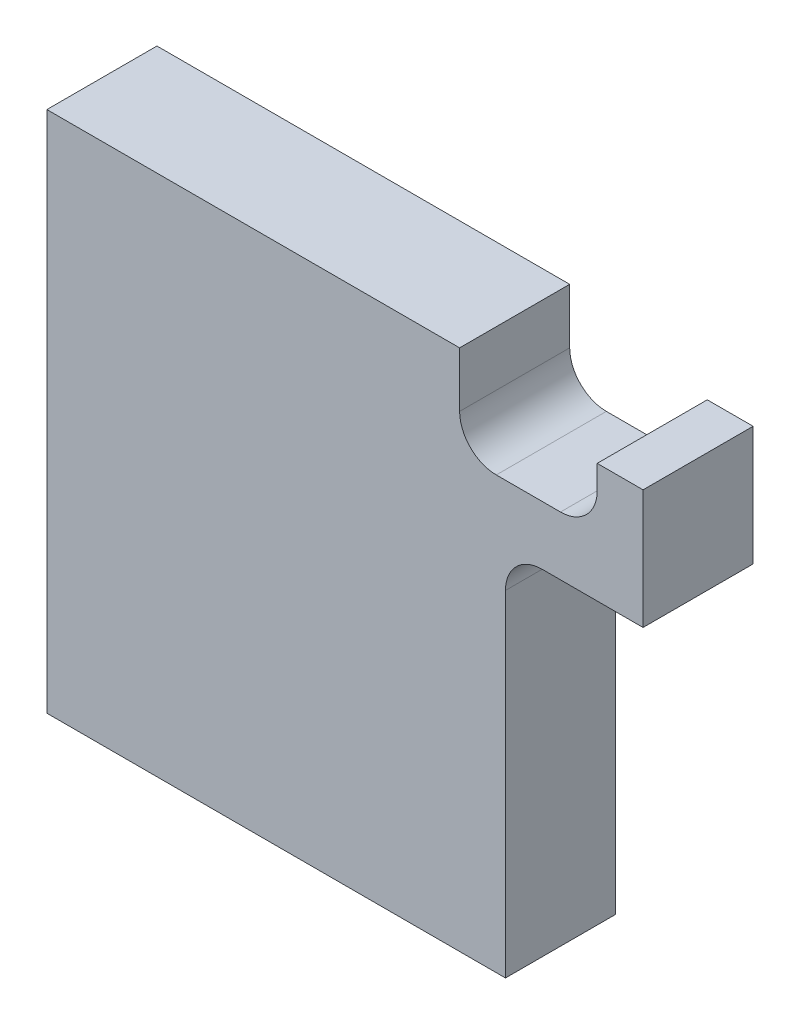
SolidWorks part; units mm, degrees
ref_plane "前视基准面" through (0, 0, 0) normal (0, 0, 1) x (1, 0, 0)
ref_plane "上视基准面" through (0, 0, 0) normal (0, 1, 0) x (1, 0, 0)
ref_plane "右视基准面" through (0, 0, 0) normal (1, 0, 0) x (0, 0, -1)
sketch "草图1" plane through (0, 0, 0) normal (0, 0, 1) x (1, 0, 0)
  line L0 (4.2193, 10.5) -> (4.2193, 4.8)
  line L1 (4.2193, 10.5) -> (8.7193, 10.5)
  line L2 (8.7193, 10.5) -> (8.7193, 9.5)
  line L3 (8.7193, 9.5) -> (10.2193, 9.5)
  line L4 (10.2193, 9.5) -> (10.2193, 10.1595)
  line L5 (10.2193, 10.1595) -> (10.7193, 10.1595)
  line L6 (10.7193, 10.1595) -> (10.7193, 8.8595)
  line L7 (9.2193, 4.8) -> (4.2193, 4.8)
  line L10 (10.7193, 8.8595) -> (9.2193, 8.8595)
  line L11 (9.2193, 8.8595) -> (9.2193, 4.8)
  line L13 (10.2193, 9.5) -> (10.2193, 8.8595) construction
  dimension "D1" = 1.3
  dimension "D2" = 0.5
  dimension "D3" = 1.5
  dimension "D5" = 5
  dimension "D6" = 1
  dimension "D8" = 1
extrude "凸台-拉伸1" add sketch "草图1" along normal blind 1.2 contours L1 L2 L3 L4 L5 L6 L10 L11 L7 L0
fillet "Fillet1" radius 0.4 3 edges at (9.2193, 8.8595, 0.6) (10.2193, 9.5, 0.6) (8.7193, 9.5, 0.6)
